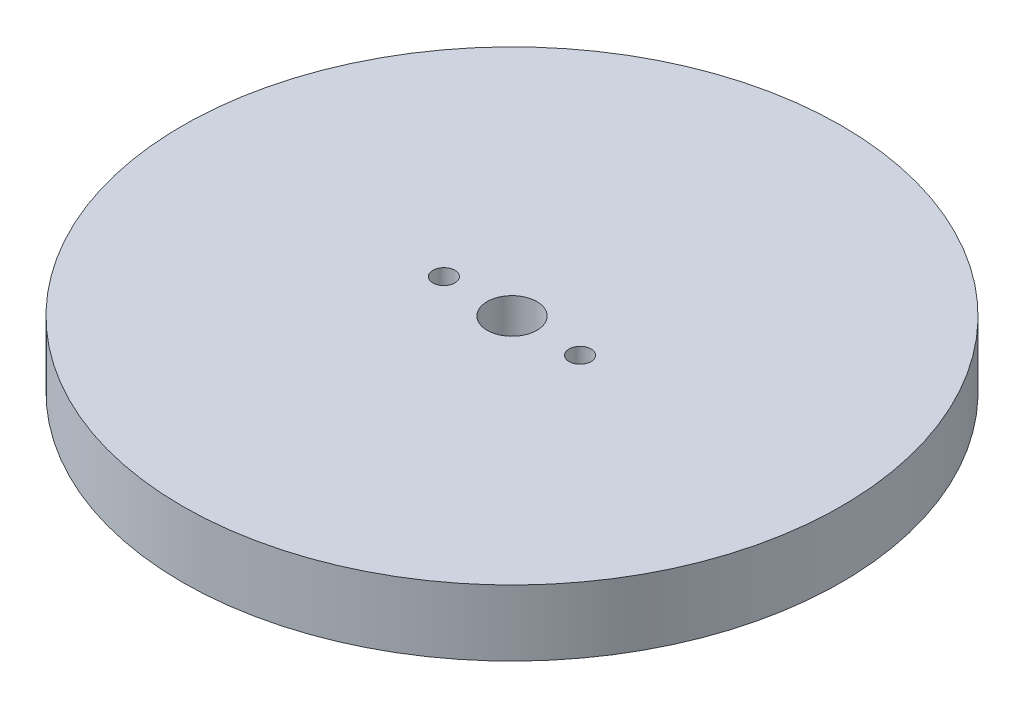
SolidWorks part; units mm, degrees
ref_plane "Front Plane" through (0, 0, 0) normal (0, 0, 1) x (1, 0, 0)
ref_plane "Top Plane" through (0, 0, 0) normal (0, 1, 0) x (1, 0, 0)
ref_plane "Right Plane" through (0, 0, 0) normal (1, 0, 0) x (0, 0, -1)
sketch "Sketch1" plane through (0, 0, 0) normal (0, 1, 0) x (1, 0, 0)
  circle A2 centre (-30.1835, -19.1453) radius 45
  circle A3 centre (-30.1835, -19.1453) radius 3.4
  circle A4 centre (-39.4835, -19.1453) radius 1.5
  circle A5 centre (-20.8835, -19.1453) radius 1.5
  dimension "D2" = 3
  dimension "D3" = 90
  dimension "D1" = 6.8
  dimension "D6" = 3
  dimension "D4" = 9.3
  dimension "D5" = 9.3
extrude "Boss-Extrude1" add sketch "Sketch1" along normal blind 9
